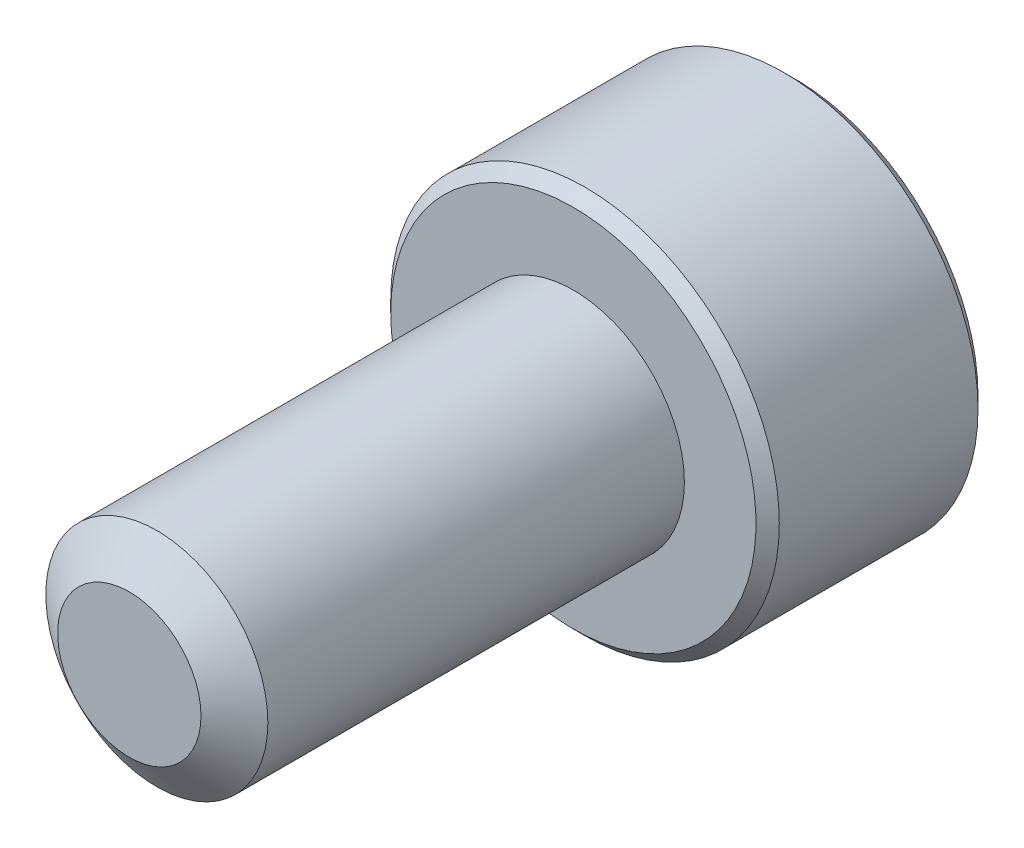
SolidWorks part; units mm, degrees
material "Plain Carbon Steel"
ref_plane "Front Plane" through (0, 0, 0) normal (0, 0, 1) x (1, 0, 0)
ref_plane "Top Plane" through (0, 0, 0) normal (0, 1, 0) x (1, 0, 0)
ref_plane "Right Plane" through (0, 0, 0) normal (1, 0, 0) x (0, 0, -1)
sketch "Sketch1" plane through (0, 0, 0) normal (0, 0, 1) x (1, 0, 0)
  circle A0 centre (0, 0) radius 2
  dimension "OD" = 4
extrude "Extrude1" add sketch "Sketch1" against normal blind 8
sketch "Sketch2" plane through (0, 0, 0) normal (0, 0, 1) x (1, 0, 0)
  circle A0 centre (0, 0) radius 2 construction
  circle A1 centre (0, 0) radius 2
curve "Helix/Spiral1" pitch 0.7 height 8.7 turns 12.4286 parameters "pitch"=0.7
sketch "Sketch3" plane through (0, 0, 0) normal (1, 0, 0) x (0, 0, -1)
  line L0 (-0.6125, 2) -> (-0.35, 1.5453)
  line L1 (-0.35, 1.5453) -> (-0.2625, 1.5453)
  line L2 (-0.2625, 1.5453) -> (0, 2)
  line L3 (-0.6125, 2) -> (0, 2)
  line L4 (-0.3063, 2) -> (-0.3063, 1.5453) construction
  line L5 (-0.4813, 1.7727) -> (-0.1313, 1.7727) construction
  line L6 (0, 2) -> (0, -2) construction
  line L7 (0, -2) -> (8, -2) construction
  point P11 (3.15, -2)
  dimension "D1" = 0.0875
  dimension "D2" = 0.35
  dimension "D3" = 60
  dimension "D4" = 3.15
sweep "Cut-Sweep1" [suppressed] cut profiles "Sketch3" path "Helix/Spiral1"
sketch "Sketch4" plane through (0, 0, 0) normal (1, 0, 0) x (0, 0, -1)
  line L0 (0.4962, 2) -> (0, 1.2913)
  line L1 (0, 1.2913) -> (0, 2)
  line L2 (0.4962, 2) -> (0, 2)
  line L3 (-0.6125, 2) -> (0, 2) construction
  line L4 (0, 0) -> (7.0209, 0) construction
  dimension "D1" = 55
  dimension "D2" = 0.254
revolve "Cut-Revolve1" cut sketch "Sketch4" angle 360 about L4
sketch "Sketch5" [suppressed] plane through (0, 0, 0) normal (1, 0, 0) x (0, 0, -1)
  line L0 (8, -0.6429) -> (8, 1.6418) construction
  line L1 (8, 2) -> (0.1203, 2)
  line L2 (8, 2) -> (8, 0)
  line L3 (8, 0) -> (0.0001, 0)
  line L4 (0.0001, 1.6698) -> (0.0001, 0)
  line L5 (0.1203, 2) -> (0.0001, 1.6698)
  line L6 (0, 0) -> (9.9695, 0) construction
  point P3 (0.0001, 2)
  point P10 (0.0001, 2)
  dimension "D1" = 0.3302
  dimension "Thread min" = 0.0001
  dimension "D3" = 20
revolve "partially thread" [suppressed] add sketch "Sketch5" angle 360 about L6
sketch "Sketch6" plane through (0, 0, -8) normal (0, 0, -1) x (-1, 0, 0)
  circle A0 centre (0, 0) radius 3.5
  dimension "head dia" = 7
extrude "Extrude2" add sketch "Sketch6" along normal blind 4
sketch "Sketch7" plane through (0, 0, -12) normal (0, 0, -1) x (-1, 0, 0)
  line L1 (0, 1.7321) -> (-1.5, 0.866)
  line L2 (-1.5, 0.866) -> (-1.5, -0.866)
  line L3 (-1.5, -0.866) -> (0, -1.7321)
  line L4 (0, -1.7321) -> (1.5, -0.866)
  line L5 (1.5, -0.866) -> (1.5, 0.866)
  line L6 (1.5, 0.866) -> (0, 1.7321)
  circle A0 centre (0, 0) radius 1.5 construction
  dimension "hex dia" = 3
extrude "Cut-Extrude1" cut sketch "Sketch7" against normal blind 2.25
sketch "Sketch8" plane through (0, 0, -12) normal (0, 0, -1) x (-1, 0, 0)
  circle A0 centre (0, 0) radius 1.7321
extrude "Cut-Extrude2" cut sketch "Sketch8" against normal through all draft 45
chamfer "Chamfer1" distance 0.21 angle 45 2 edges at (-3.5, 0, -12) (-3.5, 0, -8)
sketch "Sketch9" plane through (0, 0, 0) normal (1, 0, 0) x (0, 0, -1)
  line L0 (0, 2) -> (0, -2) construction
  line L1 (3.85, 2) -> (3.85, -2) construction
  dimension "D1" = 3.85
sketch "Sketch10" plane through (0, 0, 0) normal (1, 0, 0) x (0, 0, -1)
  line L0 (8, 2) -> (8, 0)
  line L1 (8, 2) -> (7.825, 2)
  line L2 (7.825, 2) -> (6.9966, 0)
  line L3 (8, 0) -> (6.9966, 0)
  line L4 (8, 3.29) -> (8, -3.29) construction
  dimension "D1" = 22.5
  dimension "D2" = 0.175
revolve "Revolve1" add sketch "Sketch10" angle 360 about L3
equation "\"D3@Helix/Spiral1\" = \"screw length@Extrude1\"+\"pitch@Helix/Spiral1\""
equation "\"D1@Sketch3\" = \"pitch@Helix/Spiral1\"*.125"
equation "\"D2@Sketch3\" = \"pitch@Helix/Spiral1\"*.5"
equation "\"D1@Cut-Extrude1\" = \"hex dia@Sketch7\"*.75"
equation "\"D1@Chamfer1\" = \"head dia@Sketch6\"*.03"
equation "\"D1@Sketch9\" = \"pitch@Helix/Spiral1\"*5.5"
equation "\"D2@Sketch10\" = \"pitch@Helix/Spiral1\"*.25"
equation "\"D4@Sketch3\" = \"pitch@Helix/Spiral1\"*4.50"
